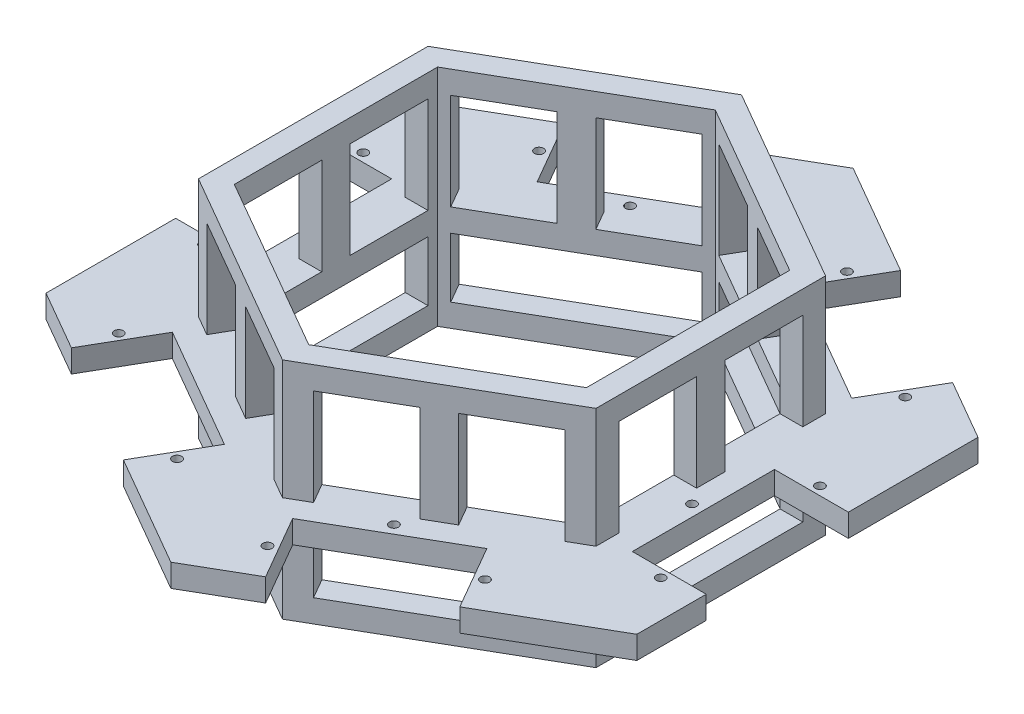
SolidWorks part; units mm, degrees
ref_plane "Front Plane" through (0, 0, 0) normal (0, 0, 1) x (1, 0, 0)
ref_plane "Top Plane" through (0, 0, 0) normal (0, 1, 0) x (1, 0, 0)
ref_plane "Right Plane" through (0, 0, 0) normal (1, 0, 0) x (0, 0, -1)
sketch "Sketch1" plane through (0, 0, 0) normal (0, 1, 0) x (1, 0, 0)
  line L1 (0, 60) -> (-51.9615, 30)
  line L2 (-51.9615, 30) -> (-51.9615, -30)
  line L3 (-51.9615, -30) -> (0, -60)
  line L4 (0, -60) -> (51.9615, -30)
  line L5 (51.9615, -30) -> (51.9615, 30)
  line L6 (51.9615, 30) -> (0, 60)
  circle A0 centre (0, 0) radius 51.9615 construction
extrude "Boss-Extrude1" add sketch "Sketch1" along normal blind 4
sketch "Sketch2" plane through (0, 4, 0) normal (0, 1, 0) x (1, 0, 0)
  line L0 (38.9615, 0) -> (38.9615, 7.2)
  line L1 (51.9615, 30) -> (0, 60) construction
  line L2 (19.4808, 33.7417) -> (13.2454, 37.3417)
  line L3 (19.4808, 33.7417) -> (34.896, 24.8417)
  line L4 (13.2454, 37.3417) -> (19.7454, 48.6)
  line L5 (34.896, 24.8417) -> (41.396, 36.1)
  line L6 (19.7454, 48.6) -> (41.396, 36.1)
  line L7 (38.9615, 7.2) -> (51.9615, 7.2)
  line L8 (51.9615, 7.2) -> (51.9615, -17.8)
  line L9 (38.9615, -17.8) -> (51.9615, -17.8)
  line L10 (38.9615, 0) -> (38.9615, -17.8)
  line L11 (19.4808, -33.7417) -> (25.7161, -30.1417)
  line L12 (25.7161, -30.1417) -> (32.2161, -41.4)
  line L13 (32.2161, -41.4) -> (10.5655, -53.9)
  line L14 (4.0655, -42.6417) -> (10.5655, -53.9)
  line L15 (19.4808, -33.7417) -> (4.0655, -42.6417)
  line L16 (-19.4808, -33.7417) -> (-13.2454, -37.3417)
  line L17 (-13.2454, -37.3417) -> (-19.7454, -48.6)
  line L18 (-19.7454, -48.6) -> (-41.396, -36.1)
  line L19 (-34.896, -24.8417) -> (-41.396, -36.1)
  line L20 (-19.4808, -33.7417) -> (-34.896, -24.8417)
  line L21 (-38.9615, 0) -> (-38.9615, -7.2)
  line L22 (-38.9615, -7.2) -> (-51.9615, -7.2)
  line L23 (-51.9615, -7.2) -> (-51.9615, 17.8)
  line L24 (-38.9615, 17.8) -> (-51.9615, 17.8)
  line L25 (-38.9615, 0) -> (-38.9615, 17.8)
  line L26 (-19.4808, 33.7417) -> (-25.7161, 30.1417)
  line L27 (-25.7161, 30.1417) -> (-32.2161, 41.4)
  line L28 (-32.2161, 41.4) -> (-10.5655, 53.9)
  line L29 (-4.0655, 42.6417) -> (-10.5655, 53.9)
  line L30 (-19.4808, 33.7417) -> (-4.0655, 42.6417)
  point P35 (0, 0)
  dimension "D1" = 6
extrude "Cut-Extrude1" cut sketch "Sketch2" against normal blind 4
sketch "Sketch3" plane through (0, 4, 0) normal (0, 1, 0) x (1, 0, 0)
  circle A0 centre (15.1963, 43.7208) radius 0.8
  circle A1 centre (39.4451, 29.7208) radius 0.8
  circle A2 centre (45.4615, 8.7) radius 0.8
  circle A3 centre (45.4615, -19.3) radius 0.8
  circle A4 centre (30.2652, -35.0208) radius 0.8
  circle A5 centre (6.0165, -49.0208) radius 0.8
  circle A6 centre (-15.1963, -43.7208) radius 0.8
  circle A7 centre (-39.4451, -29.7208) radius 0.8
  circle A8 centre (-45.4615, -8.7) radius 0.8
  circle A9 centre (-45.4615, 19.3) radius 0.8
  circle A10 centre (-30.2652, 35.0208) radius 0.8
  circle A11 centre (-6.0165, 49.0208) radius 0.8
  point P27 (0, 0)
  dimension "D1" = 6
extrude "Cut-Extrude2" cut sketch "Sketch3" against normal blind 4
sketch "Sketch4" plane through (0, 4, 0) normal (0, 1, 0) x (1, 0, 0)
  circle A1 centre (36.9615, -5.3) radius 0.8
  circle A2 centre (13.8908, -34.6596) radius 0.8
  circle A4 centre (-36.9615, 5.3) radius 0.8
  circle A5 centre (-13.8908, 34.6596) radius 0.8
  point P15 (0, 0)
extrude "Cut-Extrude3" cut sketch "Sketch4" against normal blind 4
sketch "Sketch12" plane through (0, 0, 0) normal (0, -1, 0) x (1, 0, 0)
  line L0 (34.9615, 0) -> (34.9615, 20.185)
  line L1 (34.9615, 0) -> (34.9615, -20.185)
  line L2 (17.4808, 30.2776) -> (34.9615, 20.185)
  line L3 (17.4808, 30.2776) -> (0, 40.3701)
  line L4 (17.4808, -30.2776) -> (34.9615, -20.185)
  line L5 (17.4808, -30.2776) -> (0, -40.3701)
  line L6 (-17.4808, -30.2776) -> (0, -40.3701)
  line L7 (-17.4808, -30.2776) -> (-34.9615, -20.185)
  line L8 (-34.9615, 0) -> (-34.9615, -20.185)
  line L9 (-34.9615, 0) -> (-34.9615, 20.185)
  line L10 (-17.4808, 30.2776) -> (-34.9615, 20.185)
  line L11 (-17.4808, 30.2776) -> (0, 40.3701)
  line L12 (-30.9615, 0) -> (-30.9615, -17.8756)
  line L13 (-15.4808, -26.8135) -> (-30.9615, -17.8756)
  line L14 (-15.4808, -26.8135) -> (0, -35.7513)
  line L15 (15.4808, -26.8135) -> (0, -35.7513)
  line L16 (15.4808, -26.8135) -> (30.9615, -17.8756)
  line L17 (30.9615, 0) -> (30.9615, -17.8756)
  line L18 (30.9615, 0) -> (30.9615, 17.8756)
  line L19 (15.4808, 26.8135) -> (30.9615, 17.8756)
  line L20 (15.4808, 26.8135) -> (0, 35.7513)
  line L21 (-15.4808, 26.8135) -> (0, 35.7513)
  line L22 (-15.4808, 26.8135) -> (-30.9615, 17.8756)
  line L23 (-30.9615, 0) -> (-30.9615, 17.8756)
  point P22 (0, 0)
  dimension "D1" = 6
  dimension "D2" = 4
extrude "Boss-Extrude2" add sketch "Sketch12" along normal blind 14.5
sketch "Sketch14" plane through (0, 0, 0) normal (0, -1, 0) x (1, 0, 0)
  line L0 (0, -35.7513) -> (30.9615, -17.8756) construction
  line L1 (30.9615, 17.8756) -> (0, 35.7513) construction
  line L2 (30.9615, -17.8756) -> (30.9615, 17.8756) construction
  line L3 (-30.9615, -17.8756) -> (0, -35.7513) construction
  line L4 (0, 35.7513) -> (-30.9615, 17.8756) construction
  line L5 (-30.9615, 17.8756) -> (-30.9615, -17.8756) construction
  line L6 (0, -35.7513) -> (30.9615, -17.8756)
  line L7 (30.9615, 17.8756) -> (0, 35.7513)
  line L8 (30.9615, -17.8756) -> (30.9615, 17.8756)
  line L9 (-30.9615, -17.8756) -> (0, -35.7513)
  line L10 (0, 35.7513) -> (-30.9615, 17.8756)
  line L11 (-30.9615, 17.8756) -> (-30.9615, -17.8756)
extrude "Cut-Extrude4" cut sketch "Sketch14" against normal blind 4
sketch "Sketch15" plane through (-34.9615, 0, 0) normal (-1, 0, 0) x (0, 0, 1)
  line L0 (16.185, 0) -> (-16.185, 0)
  line L6 (-16.185, 0) -> (-16.185, -10.5)
  line L7 (-16.185, -10.5) -> (16.185, -10.5)
  line L8 (16.185, -10.5) -> (16.185, 0)
extrude "Cut-Extrude6" cut sketch "Sketch15" against normal blind 4
ref_axis "Axis1" through (0, 0, 0) along (0, 1, 0)
pattern_circular "CirPattern1" count 6 every 60 about axis through (0, 0, 0) along (0, 1, 0) of "Cut-Extrude6"
sketch "Sketch17" plane through (0, 4, 0) normal (0, 1, 0) x (1, 0, 0)
  line L12 (30.9615, -17.8756) -> (30.9615, 0)
  line L13 (15.4808, -26.8135) -> (30.9615, -17.8756)
  line L14 (0, -35.7513) -> (15.4808, -26.8135)
  line L15 (-15.4808, -26.8135) -> (0, -35.7513)
  line L16 (-30.9615, -17.8756) -> (-15.4808, -26.8135)
  line L17 (-30.9615, 0) -> (-30.9615, -17.8756)
  line L18 (-30.9615, 17.8756) -> (-30.9615, 0)
  line L19 (-15.4808, 26.8135) -> (-30.9615, 17.8756)
  line L20 (0, 35.7513) -> (-15.4808, 26.8135)
  line L21 (15.4808, 26.8135) -> (0, 35.7513)
  line L22 (30.9615, 17.8756) -> (15.4808, 26.8135)
  line L23 (30.9615, 0) -> (30.9615, 17.8756)
  line L24 (30.9615, -17.8756) -> (30.9615, 0)
  line L25 (15.4808, -26.8135) -> (30.9615, -17.8756)
  line L26 (0, -35.7513) -> (15.4808, -26.8135)
  line L27 (-15.4808, -26.8135) -> (0, -35.7513)
  line L28 (-30.9615, -17.8756) -> (-15.4808, -26.8135)
  line L29 (-30.9615, 0) -> (-30.9615, -17.8756)
  line L30 (-30.9615, 17.8756) -> (-30.9615, 0)
  line L31 (-15.4808, 26.8135) -> (-30.9615, 17.8756)
  line L32 (0, 35.7513) -> (-15.4808, 26.8135)
  line L33 (15.4808, 26.8135) -> (0, 35.7513)
  line L34 (30.9615, 17.8756) -> (15.4808, 26.8135)
  line L35 (30.9615, 0) -> (30.9615, 17.8756)
  line L36 (-34.9615, 0) -> (-34.9615, -20.185)
  line L37 (-34.9615, -20.185) -> (-17.4808, -30.2776)
  line L38 (-17.4808, -30.2776) -> (0, -40.3701)
  line L39 (0, -40.3701) -> (17.4808, -30.2776)
  line L40 (17.4808, -30.2776) -> (34.9615, -20.185)
  line L41 (34.9615, -20.185) -> (34.9615, 0)
  line L42 (34.9615, 0) -> (34.9615, 20.185)
  line L43 (34.9615, 20.185) -> (17.4808, 30.2776)
  line L44 (17.4808, 30.2776) -> (0, 40.3701)
  line L45 (0, 40.3701) -> (-17.4808, 30.2776)
  line L46 (-17.4808, 30.2776) -> (-34.9615, 20.185)
  line L47 (-34.9615, 20.185) -> (-34.9615, 0)
  line L48 (-34.9615, 0) -> (-34.9615, -20.185)
  line L49 (-34.9615, -20.185) -> (-17.4808, -30.2776)
  line L50 (-17.4808, -30.2776) -> (0, -40.3701)
  line L51 (0, -40.3701) -> (17.4808, -30.2776)
  line L52 (17.4808, -30.2776) -> (34.9615, -20.185)
  line L53 (34.9615, -20.185) -> (34.9615, 0)
  line L54 (34.9615, 0) -> (34.9615, 20.185)
  line L55 (34.9615, 20.185) -> (17.4808, 30.2776)
  line L56 (17.4808, 30.2776) -> (0, 40.3701)
  line L57 (0, 40.3701) -> (-17.4808, 30.2776)
  line L58 (-17.4808, 30.2776) -> (-34.9615, 20.185)
  line L59 (-34.9615, 20.185) -> (-34.9615, 0)
  dimension "D1" = 0
  dimension "D2" = 0
extrude "Boss-Extrude3" add sketch "Sketch17" along normal blind 21
sketch "Sketch19" plane through (17.4808, 0, 30.2776) normal (0.5, 0, 0.866) x (0.866, 0, -0.5)
  line L0 (-20.185, 4) -> (-20.185, 25)
  line L1 (-20.185, 25) -> (20.185, 25)
  line L2 (20.185, 25) -> (20.185, 4)
  line L3 (-16.185, 4) -> (-16.185, 21)
  line L4 (-16.185, 21) -> (16.185, 21)
  line L5 (16.185, 21) -> (16.185, 4)
  line L6 (-16.185, 4) -> (16.185, 4)
  line M3 (-20.185, 4) -> (20.185, 4)
  dimension "D1" = 4
extrude "Cut-Extrude7" cut sketch "Sketch19" against normal blind 4 contours L5 L4 L3 M3 region at (17.4808, 12.5, 30.2776)
pattern_circular "CirPattern2" count 6 every 60 about axis through (0, 0, 0) along (0, 1, 0) of "Cut-Extrude7"
sketch "Sketch23" plane through (0, 21, 0) normal (0, -1, 0) x (1, 0, 0)
  line L1 (34.9615, 20.185) -> (0, 40.3701) construction
  line L2 (30.9615, 17.8756) -> (0, 35.7513) construction
  line L3 (15.3157, 31.5276) -> (19.6458, 29.0276)
  line L4 (19.6458, 29.0276) -> (17.6458, 25.5635)
  line L5 (13.3157, 28.0635) -> (17.6458, 25.5635)
  line L6 (15.3157, 31.5276) -> (13.3157, 28.0635)
extrude "Boss-Extrude4" add sketch "Sketch23" along normal blind 17
pattern_circular "CirPattern3" count 6 every 60 about axis through (0, 0, 0) along (0, 1, 0) of "Boss-Extrude4"
